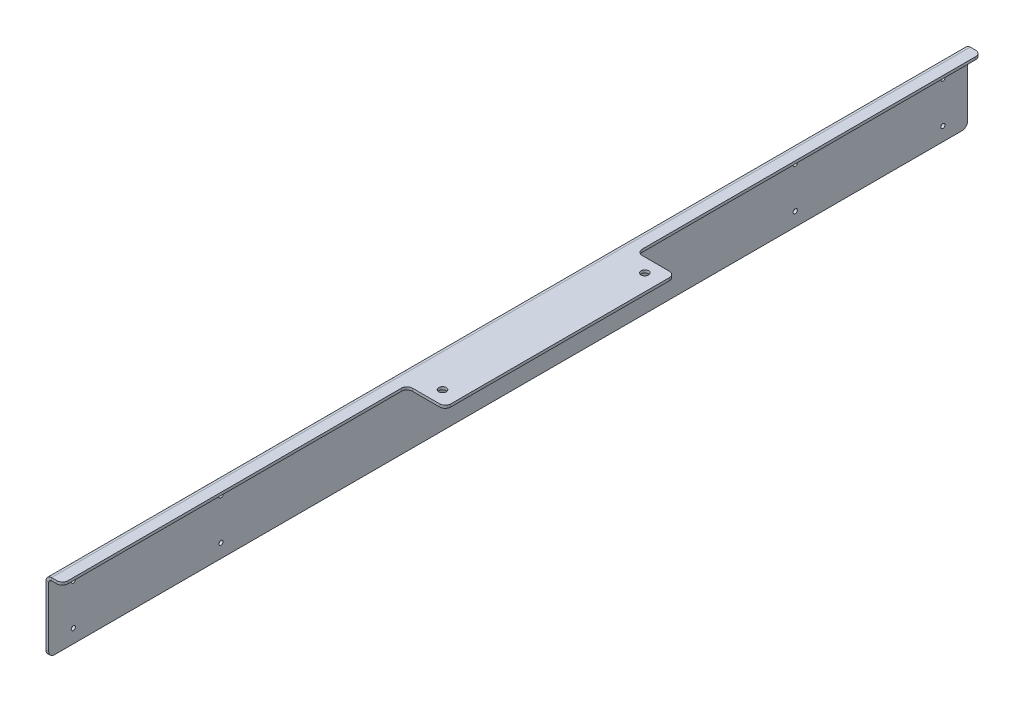
SolidWorks part; units mm, degrees
note: The reader was unsure of these and kept them because the rebuilt part matched: flange length of "Edge-Flange1".
material "5052-H32"
ref_plane "Front Plane" through (0, 0, 0) normal (0, 0, 1) x (1, 0, 0)
ref_plane "Top Plane" through (0, 0, 0) normal (0, 1, 0) x (1, 0, 0)
ref_plane "Right Plane" through (0, 0, 0) normal (1, 0, 0) x (0, 0, -1)
sketch "Sketch1" plane through (0, 0, 0) normal (1, 0, 0) x (0, 0, -1)
  line L0 (0, 0) -> (0, 82.55)
  line L3 (1066.8, 0) -> (1066.8, 82.55)
  line L20 (1066.8, 82.55) -> (0, 82.55)
  line L21 (1066.8, 0) -> (0, 0)
  dimension "D1" = 1066.8
  dimension "D2" = 82.55
  dimension "D9" = 82.55
base flange "Base-Flange1" sketch "Sketch1" thickness 3.175 reverse thickness direction no parameters "D1"=3.175
edge flange "Edge-Flange1" sketch "Sketch4" flange angle 90 flange length 63.5 flange position material inside bend radius 3.175 thickness 3.175 relief rectangular parameters "D6"=10
sketch "Sketch4" plane through (0, 82.55, 0) normal (0, 1, 0) x (0, 0, 1)
  line L0 (-1066.8, 0) -> (0, 0) construction
  line L1 (-1066.8, 0) -> (0, 0)
  line L2 (-1066.8, 0) -> (-1066.8, 60.325)
  line L3 (-1066.8, 60.325) -> (0, 60.325)
  line L4 (0, 60.325) -> (0, 0)
bend "EdgeBend1" bend radius 3.175 bend angle 90 parameters "D5"=1
sketch "Sketch9" plane through (0, 0, 0) normal (1, 0, 0) x (0, 0, -1)
  line L0 (0, 76.2) -> (1066.8, 76.2) construction
  line L1 (0, 76.2) -> (0, 0) construction
  line L2 (0, 0) -> (1066.8, 0) construction
  line L4 (1066.8, 0) -> (1066.8, 76.2) construction
  circle A0 centre (28.575, 63.5) radius 2.4574
  circle A1 centre (200.025, 63.5) radius 2.4575
  circle A2 centre (28.575, 15.875) radius 2.4574
  circle A3 centre (200.025, 15.875) radius 2.4574
  circle A4 centre (866.775, 63.5) radius 2.4575
  circle A5 centre (866.775, 15.875) radius 2.4575
  circle A6 centre (1038.225, 15.875) radius 2.4575
  circle A7 centre (1038.225, 63.5) radius 2.4575
  dimension "D5" = 4.9149
  dimension "D10" = 28.575
  dimension "D11" = 200.025
  dimension "D7" = 15.875
  dimension "D9" = 63.5
  dimension "D12" = 4.9149
  dimension "D1" = 12.7
  dimension "D2" = 28.575
  dimension "D3" = 47.625
  dimension "D4" = 171.45
  dimension "D6" = 63.5
  dimension "D8" = 15.875
extrude "Cut-Extrude1" cut sketch "Sketch9" against normal through all normal cut yes
sketch "Sketch10" plane through (0, 82.55, 0) normal (0, 1, 0) x (1, 0, 0)
  line L0 (15.875, 1066.8) -> (79.375, 1066.8)
  line L1 (60.325, 1066.8) -> (3.175, 1066.8) construction
  line L2 (15.875, 1066.8) -> (15.875, 666.75)
  line L3 (15.875, 666.75) -> (60.325, 666.75)
  line L4 (60.325, 0) -> (60.325, 1066.8) construction
  line L5 (60.325, 666.75) -> (60.325, 400.05)
  line L6 (60.325, 400.05) -> (15.875, 400.05)
  line L7 (15.875, 400.05) -> (15.875, 0)
  line L8 (3.175, 0) -> (60.325, 0) construction
  line L9 (15.875, 0) -> (79.375, 0)
  line L10 (79.375, 0) -> (79.375, 1066.8)
  line L11 (-3.175, 0) -> (-3.175, 1066.8) construction
  circle A0 centre (41.275, 650.875) radius 4.3688
  circle A1 centre (41.275, 415.925) radius 4.3688
  dimension "D8" = 8.7376
  dimension "D1" = 19.05
  dimension "D2" = 266.7
  dimension "D3" = 400.05
  dimension "D4" = 19.05
  dimension "D5" = 63.5
  dimension "D6" = 234.95
  dimension "D7" = 15.875
  dimension "D9" = 19.05
extrude "Cut-Extrude2" cut sketch "Sketch10" against normal blind 3.175 normal cut yes
fillet "Fillet1" radius 6.35 8 edges at (15.875, 80.9625, -1066.8) (15.875, 80.9625, 0) (15.875, 80.9625, -400.05) (60.325, 80.9625, -400.05) (60.325, 80.9625, -666.75) (15.875, 80.9625, -666.75) (-1.5875, 0, -1066.8) (-1.5875, 0, 0)
sketch "Bend-Lines1" [suppressed] plane through (0, 0, 0) normal (0, 1, 0) x (1, 0, 0)
sketch "Bounding-Box1" [suppressed] plane through (0, 0, 0) normal (0, 1, 0) x (1, 0, 0)
sheet metal parameters "Sheet-Metal1" thickness 3.175 parameters "D1"=3.175
flat pattern "Flat-Pattern1" [suppressed]
sketch "Bend-Lines2" plane through (0, 0, 0) normal (0, 1, 0) x (1, 0, 0)
sketch3d "Bounding-Box2" [suppressed]
  line L0 (1066.8, 0, 0) -> (0, 0, 0) construction
  line L1 (1066.8, 73.025, 0) -> (0, 73.025, 0) construction
  line L2 (1066.8, 0, 0) -> (1066.8, 73.025, 0) construction
  line L3 (0, 0, 0) -> (0, 73.025, 0) construction
sheet metal parameters "Sheet-Metal9" thickness 3.175 parameters "D1"=3.175
flat pattern "Flat-Pattern1"
sketch "Bend-Lines2" plane through (0, 0, 0) normal (1, 0, 0) x (0, 0, -1)
  line L0 (1066.8, 70.4155) -> (0, 70.4155) construction
  line L1 (1066.8, 70.4155) -> (0, 70.4155) construction
  line L2 (0, -0.1873) -> (1066.8, -0.1873) construction
  line L3 (0, -0.1873) -> (1066.8, -0.1873) construction
sketch3d "Bounding-Box2" [suppressed]
  line L0 (1066.8, -8.645, 0) -> (0, -8.645, 0) construction
  line L1 (1066.8, 118.6059, 0) -> (0, 118.6059, 0) construction
  line L2 (1066.8, -8.645, 0) -> (1066.8, 118.6059, 0) construction
  line L3 (0, -8.645, 0) -> (0, 118.6059, 0) construction
bend of the flat pattern "Flatten-<EdgeBend1>1"
sheet metal parameters "Sheet-Metal10" thickness 3.175 parameters "D1"=3.175
flat pattern "Flat-Pattern1"
sketch "Bend-Lines2" plane through (0, 0, 0) normal (1, 0, 0) x (0, 0, -1)
  line L0 (1066.7875, 70.4155) -> (0.0017, 73.5904) construction
  line L1 (1066.7875, 70.4155) -> (0.0017, 73.5904) construction
  line L2 (0, -0.1873) -> (1066.7953, -0.1873) construction
  line L3 (0, -0.1873) -> (1066.7953, -0.1873) construction
sketch3d "Bounding-Box2" [suppressed]
  line L0 (1066.7936, -9.9671, 0) -> (-0.1032, -8.6448, 0) construction
  line L1 (1066.971, 133.1585, 0) -> (0.0742, 134.4808, 0) construction
  line L2 (1066.7936, -9.9671, 0) -> (1066.971, 133.1585, 0) construction
  line L3 (-0.1032, -8.6448, 0) -> (0.0742, 134.4808, 0) construction
bend of the flat pattern "Flatten-<EdgeBend1>1"
sheet metal parameters "Sheet-Metal11" thickness 3.175 parameters "D1"=3.175
flat pattern "Flat-Pattern1"
sketch "Bend-Lines2" plane through (0, 0, 0) normal (1, 0, 0) x (0, 0, -1)
  line L0 (1066.8, 79.9405) -> (0, 79.9405) construction
  line L1 (1066.8, 79.9405) -> (0, 79.9405) construction
sketch3d "Bounding-Box2" [suppressed]
  line L0 (1066.8, 140.8311, 0) -> (0, 140.8308, 0) construction
  line L1 (1066.8, 0.0003, 0) -> (0, 0, 0) construction
  line L2 (1066.8, 140.8311, 0) -> (1066.8, 0.0003, 0) construction
  line L3 (0, 140.8308, 0) -> (0, 0, 0) construction
bend of the flat pattern "Flatten-<EdgeBend1>1"
